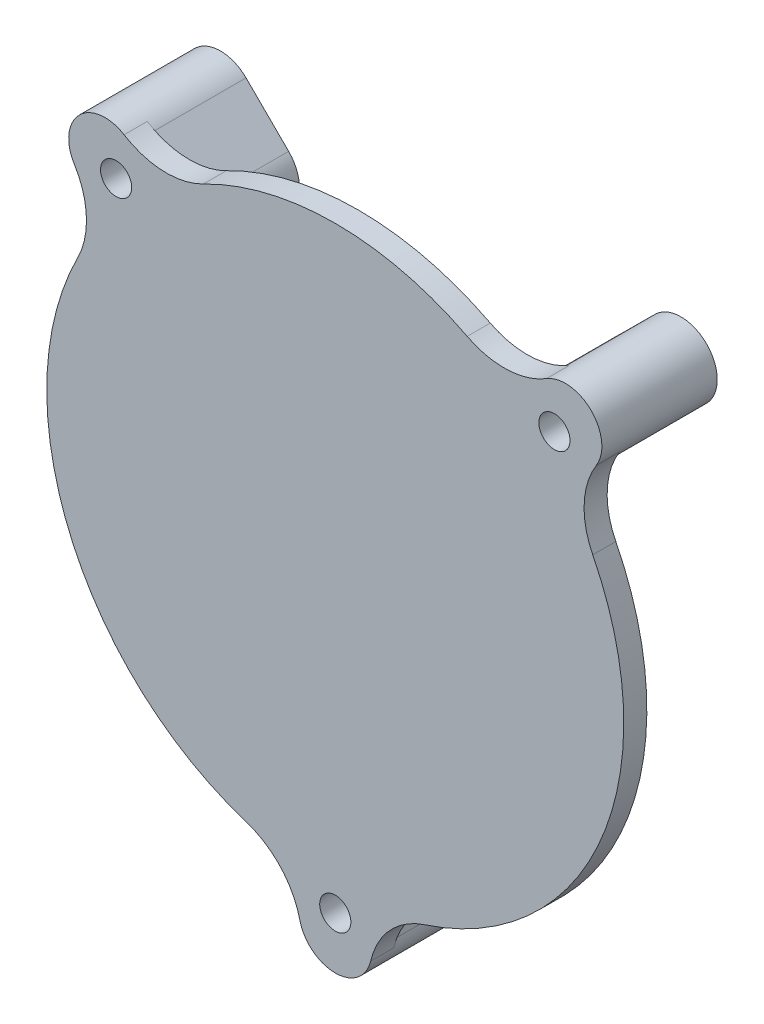
SolidWorks part; units mm, degrees
ref_plane "Front Plane" through (0, 0, 0) normal (0, 0, 1) x (1, 0, 0)
ref_plane "Top Plane" through (0, 0, 0) normal (0, 1, 0) x (1, 0, 0)
ref_plane "Right Plane" through (0, 0, 0) normal (1, 0, 0) x (0, 0, -1)
sketch "Sketch1" plane through (0, 0, 0) normal (0, 0, 1) x (1, 0, 0)
  line L0 (0, 3.85) -> (0, -1.35) construction
  line L1 (3.15, 3.85) -> (3.15, -1.35)
  line L2 (-3.15, 3.85) -> (-3.15, -1.35)
  line L3 (0, 7) -> (4.0741, 7) construction
  line L4 (0, -4.5) -> (5.7972, -4.5) construction
  circle A0 centre (0, 0) radius 1.35
  arc A1 (3.15, 3.85) -> (-3.15, 3.85) centre (0, 3.85) ccw
  arc A2 (-3.15, -1.35) -> (3.15, -1.35) centre (0, -1.35) ccw
  circle A4 centre (0, 0) radius 1.75 construction
  point P5 (0, 1.25)
  dimension "D1" = 2.7
  dimension "D2" = 6.3
  dimension "D4" = 4.5
  dimension "D3" = 7
extrude "Boss-Extrude1" add sketch "Sketch1" along normal blind 10
sketch "Sketch2" plane through (0, 0, 10) normal (0, 0, 1) x (1, 0, 0)
  line L3 (-18.99, 45.63) -> (0, 26.7666) construction
  line L4 (0, 26.7666) -> (18.99, 45.63) construction
  line L5 (0, 26.7666) -> (0, 0) construction
  circle A0 centre (0, 26.7666) radius 25
  point P2 (0, 26.1437)
  dimension "D1" = 50
extrude "Boss-Extrude2" add sketch "Sketch2" against normal blind 2
pattern_circular "CirPattern1" count 2 every 134.8 about axis through (0, 26.7666, 8) along (0, 0, 1) of "Boss-Extrude1"
pattern_circular "CirPattern2" count 2 every 225.2 about axis through (0, 26.7666, 10) along (0, 0, 1) of "Boss-Extrude1"
fillet "Fillet1" radius 7 6 edges at (-19.8175, 42.0069, 9) (-15.3783, 46.4772, 9) (15.3783, 46.4772, 9) (19.8175, 42.0069, 9) (3.15, 1.9658, 9) (-3.15, 1.9658, 9)
